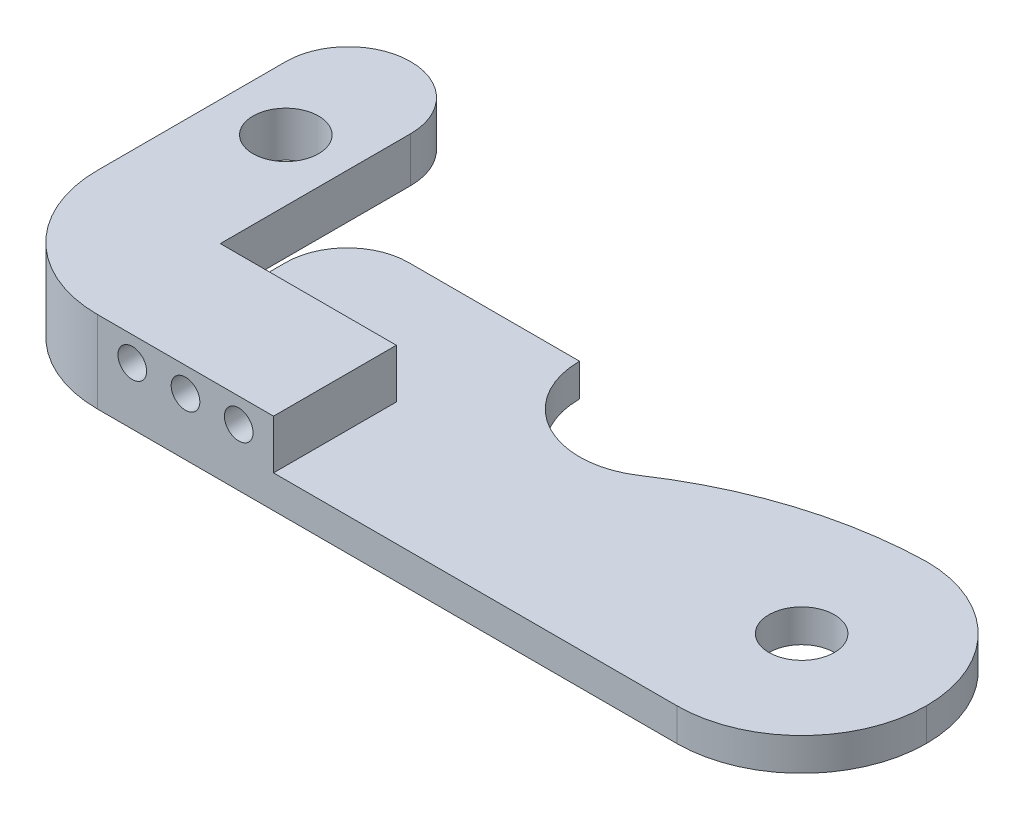
SolidWorks part; units mm, degrees
ref_plane "Front Plane" through (0, 0, 0) normal (0, 0, 1) x (1, 0, 0)
ref_plane "Top Plane" through (0, 0, 0) normal (0, 1, 0) x (1, 0, 0)
ref_plane "Right Plane" through (0, 0, 0) normal (1, 0, 0) x (0, 0, -1)
sketch "Sketch1" plane through (0, 0, 0) normal (0, 1, 0) x (1, 0, 0)
  line L0 (-13.6869, -1.9274) -> (20.7131, -1.9274)
  line L6 (-13.6869, 10.2726) -> (-13.6869, -1.9274)
  line L8 (-13.6869, 10.2726) -> (20.7131, 10.2726)
  line L10 (20.7131, 10.2726) -> (20.7131, -1.9274)
  dimension "D3" = 12.2
  dimension "D1" = 34.4
extrude "Boss-Extrude1" add sketch "Sketch1" along normal blind 1.6
sketch "Sketch8" plane through (0, 1.6, 0) normal (0, 1, 0) x (1, 0, 0)
  line L0 (5.7631, 10.2726) -> (-2.3369, 10.2726)
  line L1 (20.7131, -1.9274) -> (20.7131, 10.2726) construction
  line L2 (20.7131, -1.9274) -> (20.7131, 10.2726) construction
  line L3 (-13.6869, -1.9274) -> (20.7131, -1.9274) construction
  line L4 (20.7131, 10.2726) -> (-13.6869, 10.2726) construction
  line L6 (-13.6869, 10.2726) -> (-13.6869, -1.9274) construction
  circle A0 centre (14.6131, 4.1726) radius 1.6
  arc A1 (-2.3369, 10.2726) -> (5.7631, 10.2726) centre (1.7131, 10.2726) ccw
  dimension "D1" = 3.2
  dimension "D5" = 8.1
  dimension "D2" = 6.1
  dimension "D4" = 6.1
  dimension "D6" = 19
extrude "Cut-Extrude3" cut sketch "Sketch8" against normal through all
fillet "Fillet2" radius 3 1 edges at (-13.6869, 0.8, -10.2726)
fillet "Fillet3" radius 6.1 2 edges at (20.7131, 0.8, 1.9274) (20.7131, 0.8, -10.2726)
sketch "Sketch2" plane through (0, 1.6, 0) normal (0, 1, 0) x (1, 0, 0)
  line L1 (-13.6869, -1.9274) -> (-5.0869, -1.9274)
  line L2 (-13.6869, -1.9274) -> (-13.6869, 4.0726)
  line L3 (-13.6869, 4.0726) -> (-5.0869, 4.0726)
  line L4 (-5.0869, -1.9274) -> (-5.0869, 4.0726)
  line L5 (-13.6869, 7.2726) -> (-13.6869, -1.9274) construction
  dimension "D1" = 8.6
  dimension "D2" = 6
extrude "Boss-Extrude2" add sketch "Sketch2" along normal blind 2.4
sketch "Sketch3" plane through (0, 0, 1.9274) normal (0, 0, 1) x (1, 0, 0)
  line L0 (-5.0869, 4) -> (-5.0869, 1.6) construction
  line L1 (-13.6869, 4) -> (-5.0869, 4) construction
  line L2 (-13.6869, 4) -> (-5.0869, 4) construction
  line L3 (-13.6869, 4) -> (-13.6869, 0) construction
  circle A0 centre (-11.9869, 2.8) radius 0.7
  circle A1 centre (-6.7869, 2.8) radius 0.7
  circle A2 centre (-9.3869, 2.8) radius 0.7
  dimension "D1" = 1.4
  dimension "D2" = 1.4
  dimension "D4" = 1.4
  dimension "D3" = 1.7
  dimension "D5" = 1.2
  dimension "D6" = 1.2
  dimension "D7" = 2.6
  dimension "D8" = 1.2
  dimension "D9" = 1.7
  dimension "D10" = 2.6
extrude "Cut-Extrude1" cut sketch "Sketch3" against normal up to surface (6 mm away) up to face at (-9.3869, 2.8, -4.0726)
ref_plane "Plane1" through (0, 1.8, 0) normal (0, 1, 0) x (1, 0, 0)
sketch "Sketch4" plane through (0, 0, 0) normal (0, -1, 0) x (1, 0, 0)
  line L0 (-13.6869, 1.9274) -> (-13.6869, -4.1726)
  line L2 (-13.6869, -4.1726) -> (-19.7869, -4.1726)
  arc A0 (-13.6869, 1.9274) -> (-19.7869, -4.1726) centre (-13.6869, -4.1726) ccw
  dimension "D1" = 6.1
extrude "Boss-Extrude3" add sketch "Sketch4" against normal blind 4 separate body
sketch "Sketch5" plane through (0, 0, -4.1726) normal (0, 0, -1) x (-1, 0, 0)
  line L0 (19.7869, 4) -> (19.7869, 0) construction
  line L1 (13.6869, 4) -> (19.7869, 4)
  line L2 (13.6869, 4) -> (13.6869, 1.8)
  line L3 (13.6869, 1.8) -> (19.7869, 1.8)
  line L4 (19.7869, 4) -> (19.7869, 1.8)
extrude "Boss-Extrude4" add sketch "Sketch5" along normal blind 9.2
sketch "Sketch6" plane through (0, 4, 0) normal (0, 1, 0) x (1, 0, 0)
  line L0 (-19.7869, 13.3726) -> (-13.6869, 13.3726) construction
  line L1 (-19.7869, 13.3726) -> (-13.6869, 13.3726)
  arc A0 (-13.6869, 13.3726) -> (-19.7869, 13.3726) centre (-16.7369, 13.3726) ccw
extrude "Boss-Extrude5" add sketch "Sketch6" against normal up to surface (2.2 mm away) up to face at (-16.7369, 1.8, -8.7726)
sketch "Sketch7" plane through (0, 4, 0) normal (0, 1, 0) x (1, 0, 0)
  line L0 (-5.0869, -1.9274) -> (14.6131, -1.9274) construction
  line L2 (-19.7869, 13.3726) -> (-19.7869, 4.1726) construction
  circle A0 centre (-16.6869, 10.2726) radius 1.6
  dimension "D2" = 3.2
  dimension "D1" = 12.2
  dimension "D3" = 3.1
extrude "Cut-Extrude2" cut sketch "Sketch7" against normal up to surface (2.2 mm away) up to face at (-16.7369, 1.8, -9.5351)
fillet "Fillet1" radius 20 1 edges at (5.7631, 0.8, -10.2726)
